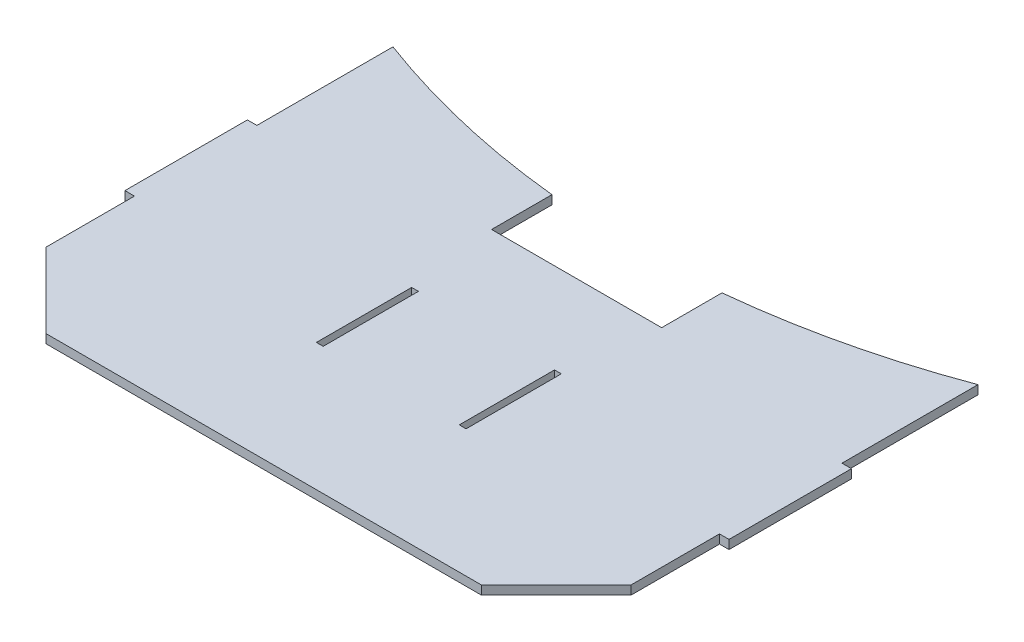
SolidWorks part; units mm, degrees
ref_plane "Front Plane" through (0, 0, 0) normal (0, 0, 1) x (1, 0, 0)
ref_plane "Top Plane" through (0, 0, 0) normal (0, 1, 0) x (1, 0, 0)
ref_plane "Right Plane" through (0, 0, 0) normal (1, 0, 0) x (0, 0, -1)
sketch "Sketch1" plane through (0, 0, 0) normal (0, 1, 0) x (1, 0, 0)
  line L0 (-43, 2) -> (-43, -20) construction
  line L1 (-43, 31) -> (43, 31)
  line L2 (-43, 31) -> (-43, -20)
  line L3 (-32, -31) -> (32, -31)
  line L4 (43, 31) -> (43, -20)
  line L5 (-43, 31) -> (43, -31) construction
  line L6 (-43, -31) -> (43, 31) construction
  line L7 (43, 2) -> (43, -20) construction
  line L8 (-55, 0) -> (55, 0) construction
  line L9 (-2, -31) -> (32, -31) construction
  line L10 (-2, -31) -> (-32, -31) construction
  line L11 (-43, -31) -> (-32, -31) construction
  line L12 (-43, -20) -> (-43, -31) construction
  line L13 (32, -31) -> (43, -31) construction
  line L14 (43, -20) -> (43, -31) construction
  line L15 (-43, -20) -> (-32, -31)
  line L16 (43, -20) -> (32, -31)
  line L17 (0, -55) -> (0, 55) construction
  point P0 (0, 0)
  dimension "D1" = 86
  dimension "D2" = 62
  dimension "D3" = 20
  dimension "D4" = 20
  dimension "D5" = 32
  dimension "D6" = 32
extrude "Boss-Extrude1" add sketch "Sketch1" along normal blind 1.3
sketch "Sketch2" plane through (0, 0, 0) normal (0, 1, 0) x (1, 0, 0)
  line L0 (43, -20) -> (43, 31) construction
  line L1 (43, -7) -> (44.4, -7)
  line L2 (43, -7) -> (43, 11)
  line L3 (43, 11) -> (44.4, 11)
  line L4 (44.4, -7) -> (44.4, 11)
  line L5 (-43, 31) -> (-43, -20) construction
  line L6 (43, 31) -> (-43, 31) construction
  line L7 (-43, -7) -> (-44.4, -7)
  line L8 (-43, -7) -> (-43, 11)
  line L9 (-43, 11) -> (-44.4, 11)
  line L10 (-44.4, -7) -> (-44.4, 11)
  line L11 (0, -0.715) -> (0, 0.715) construction
  line L12 (-12.5, 31) -> (12.5, 31)
  line L13 (-12.5, 31) -> (-12.5, 15)
  line L14 (-12.5, 15) -> (12.5, 15)
  line L15 (12.5, 31) -> (12.5, 15)
  line L16 (-12.5, 31) -> (12.5, 15) construction
  line L17 (-12.5, 15) -> (12.5, 31) construction
  point P14 (0, 23)
  dimension "D1" = 1.4
  dimension "D2" = 1.4
  dimension "D3" = 18
  dimension "D4" = 18
  dimension "D5" = 20
  dimension "D6" = 20
  dimension "D7" = 16
  dimension "D8" = 25
extrude "Boss-Extrude2" add sketch "Sketch2" along normal blind 1.3 contours L4 L3 L2 L1 | L10 L9 L8 L7
extrude "Cut-Extrude1" cut sketch "Sketch2<3>" along normal through all contours L15 L14 L13 L12
sketch "Sketch2<3>" plane through (0, 0, 0) normal (0, 1, 0) x (1, 0, 0) same geometry as "Sketch2"
sketch "Sketch6" plane through (0, 1.3, 0) normal (0, 1, 0) x (1, 0, 0)
  line L0 (-43, 31) -> (43, 31)
  arc A0 (-43, 31) -> (43, 31) centre (0, 146.1198) ccw
extrude "Cut-Extrude2" cut sketch "Sketch6" against normal through all
sketch "Sketch7" plane through (0, 1.3, 0) normal (0, 1, 0) x (1, 0, 0)
  line L0 (0, -0.715) -> (0, 0.715) construction
  line L1 (-11, 1.75) -> (-10, 1.75)
  line L2 (-11, 1.75) -> (-11, -12.25)
  line L3 (-11, -12.25) -> (-10, -12.25)
  line L4 (-10, 1.75) -> (-10, -12.25)
  line L5 (10, 1.75) -> (11, 1.75)
  line L6 (10, 1.75) -> (10, -12.25)
  line L7 (10, -12.25) -> (11, -12.25)
  line L8 (11, 1.75) -> (11, -12.25)
  line L9 (-12.5, 15) -> (12.5, 15) construction
  dimension "D1" = 1
  dimension "D2" = 1
  dimension "D3" = 10
  dimension "D4" = 10
  dimension "D5" = 14
  dimension "D6" = 14
  dimension "D7" = 13.25
  dimension "D8" = 13.25
extrude "Cut-Extrude3" cut sketch "Sketch7" against normal through all
